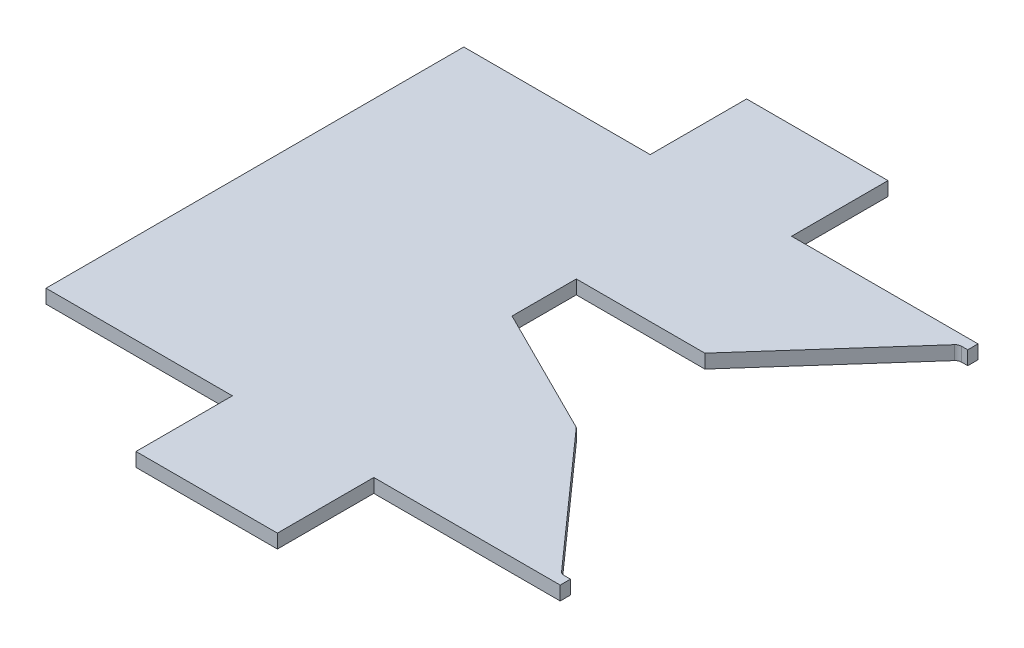
SolidWorks part; units mm, degrees
ref_plane "Front Plane" through (0, 0, 0) normal (0, 0, 1) x (1, 0, 0)
ref_plane "Top Plane" through (0, 0, 0) normal (0, 1, 0) x (1, 0, 0)
ref_plane "Right Plane" through (0, 0, 0) normal (1, 0, 0) x (0, 0, -1)
sketch "Sketch2" plane through (0, 0, 0) normal (0, 1, 0) x (1, 0, 0)
  line L2 (0, 0) -> (0, 65)
  line L3 (0, 65) -> (58, 65)
  line L4 (160, 0) -> (160, 65)
  line L8 (0, 0) -> (160, 0)
  line L9 (102, 65) -> (160, 65)
  line L11 (102, 65) -> (102, 95)
  line L12 (58, 65) -> (58, 95)
  line L13 (58, 95) -> (102, 95)
  dimension "D1" = 65
  dimension "D2" = 160
  dimension "D3" = 44
  dimension "D4" = 30
extrude "Boss-Extrude1" add sketch "Sketch2" along normal blind 4.3
mirror "Mirror1" about plane through (0, 4.3, 0) normal (0, 0, -1) of bodies 101
sketch "Sketch3" plane through (0, 4.3, 0) normal (0, 1, 0) x (1, 0, 0)
  line L0 (160, 61.8) -> (160, -61.8)
  line L1 (120.0126, 20) -> (157.1565, 61.8)
  line L3 (80.0126, 0) -> (80.0126, 20)
  line L4 (80.0126, 20) -> (120.0126, 20)
  line L12 (160, 65) -> (102, 65)
  line L13 (102, 65) -> (102, 95)
  line L15 (102, 95) -> (58, 95)
  line L16 (58, 65) -> (0, 65)
  line L17 (0, 65) -> (0, -65)
  line L18 (0, -65) -> (58, -65)
  line L20 (58, 95) -> (58, 65)
  line L22 (102, -65) -> (160, -65)
  line L23 (160, -65) -> (160, 65)
  line L36 (58, -65) -> (58, -95)
  line L38 (58, -95) -> (102, -95)
  line L39 (58, -95) -> (102, -95)
  line L40 (102, -95) -> (102, -65)
  line L42 (160, -61.8) -> (157.1556, -61.8)
  line L45 (160, 61.8) -> (157.1565, 61.8)
  line L48 (80.0126, 0) -> (120, -20)
  line L49 (120, -20) -> (157.1556, -61.8)
  line M24 (160, -65) -> (160, 65)
  dimension "D2" = 130
  dimension "D3" = 20
  dimension "D4" = 40
  dimension "D1" = 0
extrude "Cut-Extrude1" cut sketch "Sketch3" against normal blind 4.5 contours L48 L49 L1 L4 L3 M24 region at (132.7054, 4.3, -1.1594)
fillet "Fillet1" radius 2 2 edges at (157.1565, 2.15, -61.8) (157.1556, 2.15, 61.8)
ref_axis "Axis1" through (80, 4.3, 95) along (0, 0, -1)
sketch "Sketch4" plane through (0, 4.3, 0) normal (0, 1, 0) x (1, 0, 0)
  line L0 (80, -95) -> (80, 95)
  line L1 (102, -95) -> (58, -95) construction
  line L2 (102, 95) -> (58, 95) construction
